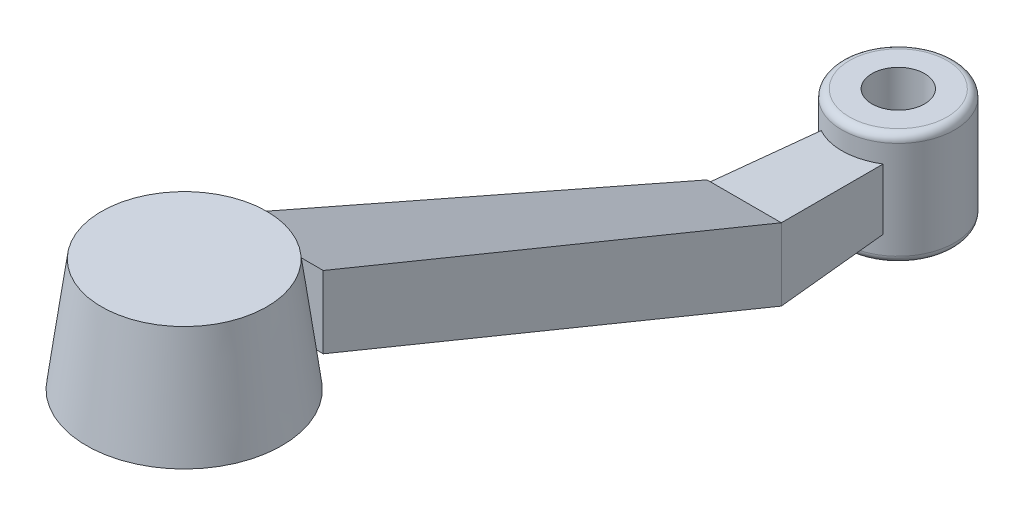
SolidWorks part; units mm, degrees
ref_plane "Alzado" through (0, 0, 0) normal (0, 0, 1) x (1, 0, 0)
ref_plane "Planta" through (0, 0, 0) normal (0, 1, 0) x (1, 0, 0)
ref_plane "Vista lateral" through (0, 0, 0) normal (1, 0, 0) x (0, 0, -1)
sketch "Croquis4" plane through (0, 0, 0) normal (0, 1, 0) x (1, 0, 0)
  circle A0 centre (0, 0) radius 7
  circle A1 centre (0, 0) radius 15
  dimension "D1" = 30
  dimension "D2" = 14
extrude "Saliente-Extruir1" add sketch "Croquis4" along normal blind 30
fillet "Redondeo1" radius 2 2 edges at (0, 0, 15) (0, 30, 15)
ref_plane "Plano1" through (0, 15, 0) normal (0, -1, 0) x (-1, 0, 0)
sketch "Croquis7" plane through (0, 15, 0) normal (0, -1, 0) x (-1, 0, 0)
  line L0 (0, 0) -> (0, 50000) construction
  line L1 (0, 0) -> (50000, 0) construction
ref_plane "Plano2" through (0, 0, 15) normal (0, 0, 1) x (1, 0, 0)
sketch "Croquis8" plane through (0, 0, 15) normal (0, 0, 1) x (1, 0, 0)
  line L14 (0, 0) -> (0, 50000) construction
  line L15 (17.8455, 15) -> (-49982.1545, 15) construction
  line L17 (2.7195, 15) -> (-49997.2805, 15) construction
  line L21 (-7.6301, 23.2051) -> (8.5221, 23.2051)
  line L22 (-7.6301, 23.2051) -> (-7.6301, 6.724)
  line L23 (-7.6301, 6.724) -> (8.5221, 6.724)
  line L24 (8.5221, 23.2051) -> (8.5221, 6.724)
extrude "Saliente-Extruir2" add sketch "Croquis8" along normal blind 26 draft 3 and the other way blind 5 draft 3 draft outward yes
sketch "Croquis9" plane through (0, 0, 0) normal (1, 0, 0) x (0, 0, -1)
  line L0 (-41, 24.5677) -> (-41, 5.3614)
  line L1 (-41, 24.5677) -> (-166, 77.627)
  line L2 (-41, 5.3614) -> (-166, 58.4208)
  line L3 (-166, 77.627) -> (-166, 58.4208)
  line L4 (-12.4357, 23.0707) -> (-41, 24.5677) construction
  dimension "D1" = 160
  dimension "D2" = 166
ref_plane "Plano3" through (0, 0, 207) normal (0, 0, 1) x (1, 0, 0)
extrude "Saliente-Extruir4" add sketch "Croquis9" along normal mid plane 42.8 contours L1 L3 L2 L0
ref_plane "Plano4" through (0, 50, 0) normal (0, 1, 0) x (1, 0, 0)
sketch "Croquis12" plane through (0, 50, 0) normal (0, 1, 0) x (1, 0, 0)
  line L8 (9.8847, -41) -> (13, -166)
  line L9 (0, -200000) -> (0, 250000) construction
  line L10 (9.8847, -41) -> (33.3501, -41)
  line L11 (33.3501, -41) -> (33.3501, -166)
  line L12 (33.3501, -166) -> (13, -166)
  point P0 (23.175, -166)
  dimension "D1" = 125
  dimension "D2" = 20.3501
  dimension "D3" = 23.175
extrude "Cortar-Extruir2" cut sketch "Croquis12" against normal blind 100.8 and the other way blind 100.8
mirror "Simetría3" about plane through (0, 0, 0) normal (1, 0, 0) of "Cortar-Extruir2"
sketch "Croquis14" plane through (0, 0, 0) normal (1, 0, 0) x (0, 0, -1)
  line L0 (-190, 79.9909) -> (-190, 50079.9909) construction
  line L1 (-190, 85.7541) -> (-212, 85.7541)
  line L2 (-212, 85.7541) -> (-216, 55.7541)
  line L3 (-216, 55.7541) -> (-190, 55.7541)
  line L4 (-190, 55.7541) -> (-190, 85.7541)
  point P6 (-203, 55.7541)
  point P8 (-269.1817, 95.2595)
  point P11 (-201, 85.7541)
  dimension "D1" = 24
  dimension "D2" = 13
  dimension "D3" = 11
  dimension "D4" = 30
revolve "Revolución1" add sketch "Croquis14" angle 360 about L0
